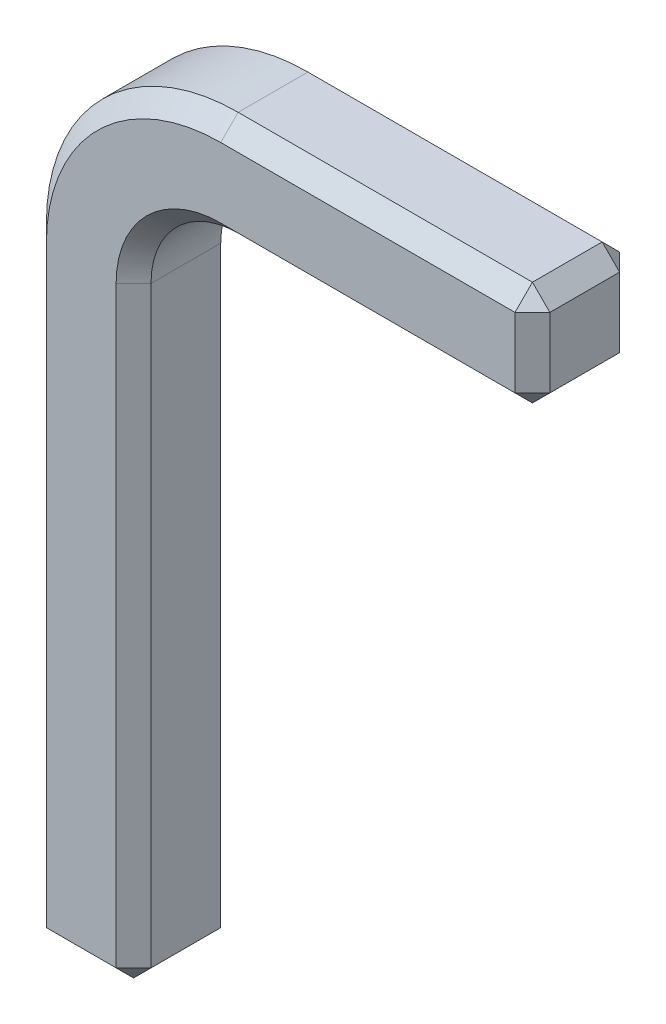
SolidWorks part; units mm, degrees
ref_plane "Front" through (0, 0, 0) normal (0, 0, 1) x (1, 0, 0)
ref_plane "Top" through (0, 0, 0) normal (0, 1, 0) x (1, 0, 0)
ref_plane "Right" through (0, 0, 0) normal (1, 0, 0) x (0, 0, -1)
sketch "Sketch1" plane through (0, 0, 0) normal (0, 0, 1) x (1, 0, 0)
  line L0 (-0.6, 0) -> (-0.6, 3.5)
  line L1 (0, 0) -> (0, 3.5)
  line L2 (0.5, 4) -> (2.2877, 4)
  line L3 (0.5, 4.6) -> (2.2877, 4.6)
  line L4 (2.2877, 4.6) -> (2.2877, 4)
  line L5 (-0.6, 0) -> (0, 0)
  arc A0 (0, 3.5) -> (0.5, 4) centre (0.5, 3.5) cw
  arc A1 (-0.6, 3.5) -> (0.5, 4.6) centre (0.5, 3.5) cw
  point P0 (0.8697, 4)
  dimension "D1" = 4
  dimension "D3" = 0.5
  dimension "D2" = 0.6
extrude "Boss-Extrude1" add sketch "Sketch1" along normal mid plane 0.6
chamfer "Chamfer1" distance 0.1 angle 45 20 edges at (-0.6, 0, 0) (-0.3, 0, 0.3) (0, 0, 0) (-0.3, 0, -0.3) (2.2877, 4, 0) (2.2877, 4.3, 0.3) (2.2877, 4.6, 0) (2.2877, 4.3, -0.3) (0, 1.75, -0.3) (0.1464, 3.8536, -0.3) (1.3938, 4, -0.3) (1.3938, 4.6, -0.3) (-0.2778, 4.2778, -0.3) (-0.6, 1.75, -0.3) (-0.6, 1.75, 0.3) (-0.2778, 4.2778, 0.3) (1.3938, 4.6, 0.3) (0, 1.75, 0.3) (0.1464, 3.8536, 0.3) (1.3938, 4, 0.3)
sketch "Sketch2" plane through (0, 0, 0) normal (0, 0, 1) x (1, 0, 0)
  line L0 (-0.3, 0) -> (-0.3, 3.2516) construction
  line L1 (-0.1, 0) -> (-0.5, 0) construction
  point P4 (-0.3, 3.2516)
